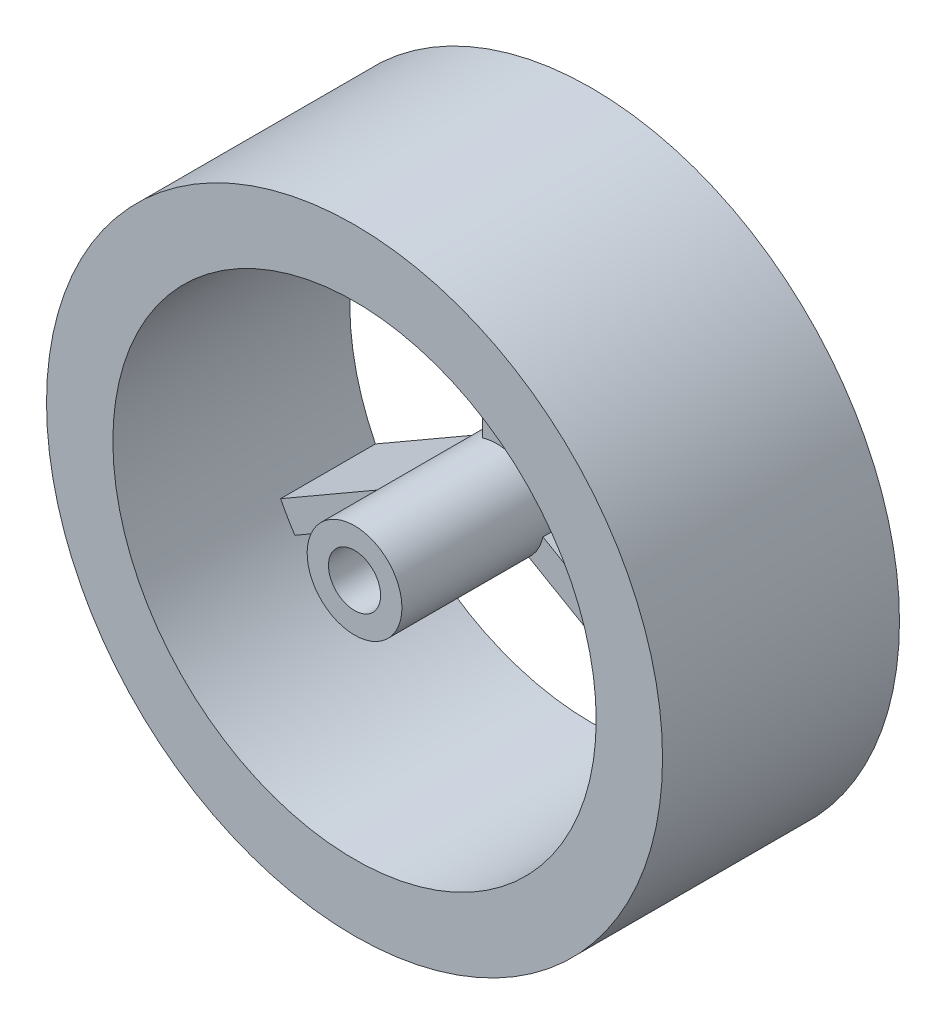
SolidWorks part; units mm, degrees
ref_plane "前视基准面" through (0, 0, 0) normal (0, 0, 1) x (1, 0, 0)
ref_plane "上视基准面" through (0, 0, 0) normal (0, 1, 0) x (1, 0, 0)
ref_plane "右视基准面" through (0, 0, 0) normal (1, 0, 0) x (0, 0, -1)
other "Configuration Table"
sketch "草图1" plane through (0, 0, 0) normal (0, 0, 1) x (1, 0, 0)
  circle A0 centre (0, 0) radius 25.5
  circle A1 centre (0, 0) radius 32.5
  dimension "D1" = 51
  dimension "D2" = 65
extrude "凸台-拉伸1" add sketch "草图1" along normal blind 25
sketch "草图2" plane through (0, 0, 0) normal (0, 0, 1) x (1, 0, 0)
  line L0 (-1.5, 4.7697) -> (-1.5, 25.4558)
  line L1 (1.5, 4.7697) -> (1.5, 25.4558)
  line L2 (0, 0) -> (0, 25.5) construction
  line L3 (4.8807, -1.0858) -> (22.7954, -11.4289)
  line L4 (3.3807, -3.6839) -> (21.2954, -14.027)
  line L5 (-3.3807, -3.6839) -> (-21.2954, -14.027)
  line L6 (-4.8807, -1.0858) -> (-22.7954, -11.4289)
  circle A0 centre (0, 0) radius 2.75
  circle A1 centre (0, 0) radius 5
  circle A2 centre (0, 0) radius 25.5
  circle A3 centre (0, 0) radius 25.5 construction
  point P13 (8.058, -0.7346)
  point P14 (0, 0)
  point P22 (0, 0)
  dimension "D1" = 5.5
  dimension "D2" = 10
  dimension "D3" = 3
  dimension "D4" = 3
extrude "凸台-拉伸2" add sketch "草图2" along normal blind 10 contours A1 L2 A2 L0 | L2 A1 L1 A2 | L6 A2 L5 A1 | L4 A2 L3 A1 region at (-0.7511, 15.2045, 0) region at (-13.1675, -7.6023, 0) region at (0.7511, 15.2045, 0) region at (13.1675, -7.6023, 0)
extrude "凸台-拉伸3" add sketch "草图2<3>" along normal blind 25 contours A0 A1 region at (0, 4.8586, 0)
sketch "草图2<3>" plane through (0, 0, 0) normal (0, 0, 1) x (1, 0, 0) same geometry as "草图2"
